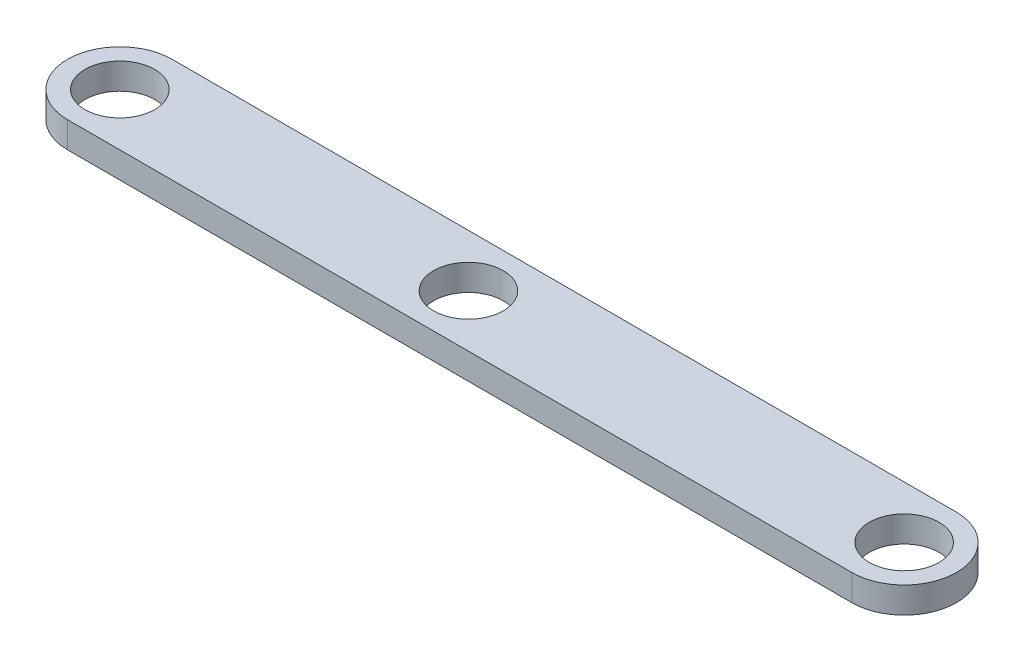
SolidWorks part; units mm, degrees
ref_plane "Front Plane" through (0, 0, 0) normal (0, 0, 1) x (1, 0, 0)
ref_plane "Top Plane" through (0, 0, 0) normal (0, 1, 0) x (1, 0, 0)
ref_plane "Right Plane" through (0, 0, 0) normal (1, 0, 0) x (0, 0, -1)
sketch "Sketch1" plane through (0, 0, 0) normal (0, 1, 0) x (1, 0, 0)
  line L0 (0, 6) -> (90, 6)
  line L1 (0, -6) -> (90, -6)
  circle A0 centre (0, 0) radius 4
  circle A1 centre (90, 0) radius 4
  arc A2 (0, 6) -> (0, -6) centre (0, 0) ccw
  arc A3 (90, -6) -> (90, 6) centre (90, 0) ccw
  circle A4 centre (0, 0) radius 6 construction
  circle A5 centre (90, 0) radius 6 construction
  dimension "D1" = 90
  dimension "D2" = 8
  dimension "D3" = 8
  dimension "D4" = 2
extrude "Boss-Extrude1" add sketch "Sketch1" along normal blind 3
sketch "Sketch2" plane through (0, 3, 0) normal (0, 1, 0) x (1, 0, 0)
  circle A0 centre (40, 0) radius 4
extrude "Cut-Extrude1" cut sketch "Sketch2" against normal through all
